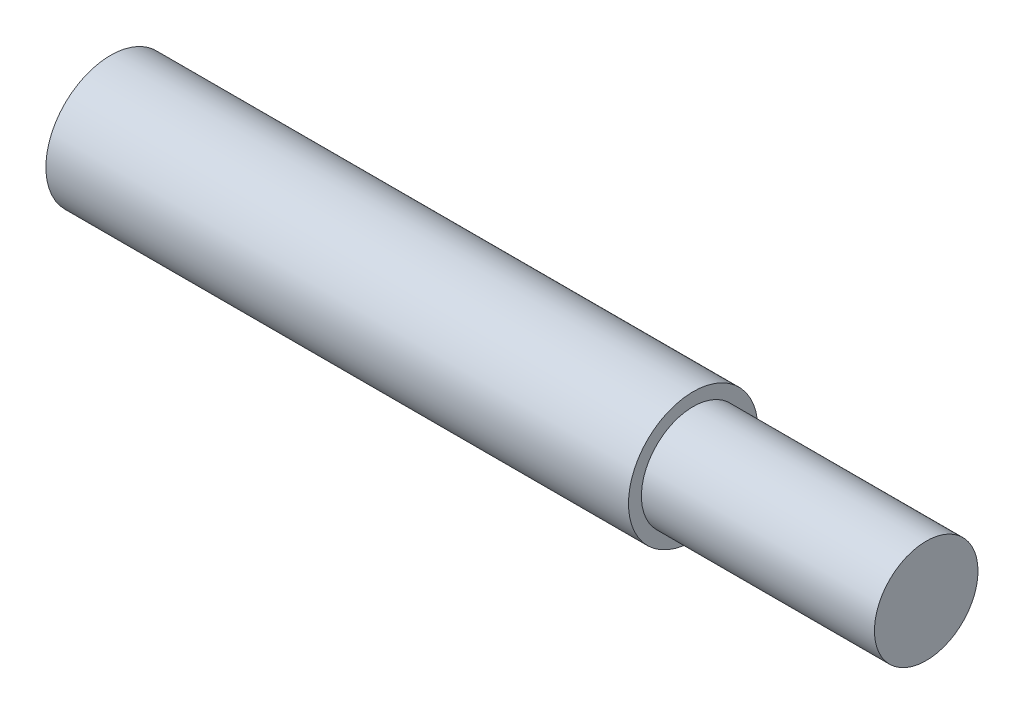
SolidWorks part; units mm, degrees
ref_plane "Front Plane" through (0, 0, 0) normal (0, 0, 1) x (1, 0, 0)
ref_plane "Top Plane" through (0, 0, 0) normal (0, 1, 0) x (1, 0, 0)
ref_plane "Right Plane" through (0, 0, 0) normal (1, 0, 0) x (0, 0, -1)
sketch "Sketch1" plane through (0, 0, 0) normal (1, 0, 0) x (0, 0, -1)
  circle A0 centre (0, 0) radius 3.175
  circle A1 centre (0, 0) radius 2.54
  dimension "D1" = 6.35
  dimension "D2" = 5.08
extrude "Boss-Extrude1" add sketch "Sketch1" along normal blind 11.43 contours A0 | A1 region at (0, 0, 0)
extrude "Boss-Extrude2" add sketch "Sketch1<3>" against normal blind 28.575 contours A0 | A1 region at (0, 0, 3.0852) region at (0, 0, 0)
sketch "Sketch1<3>" plane through (0, 0, 0) normal (1, 0, 0) x (0, 0, -1) same geometry as "Sketch1"
